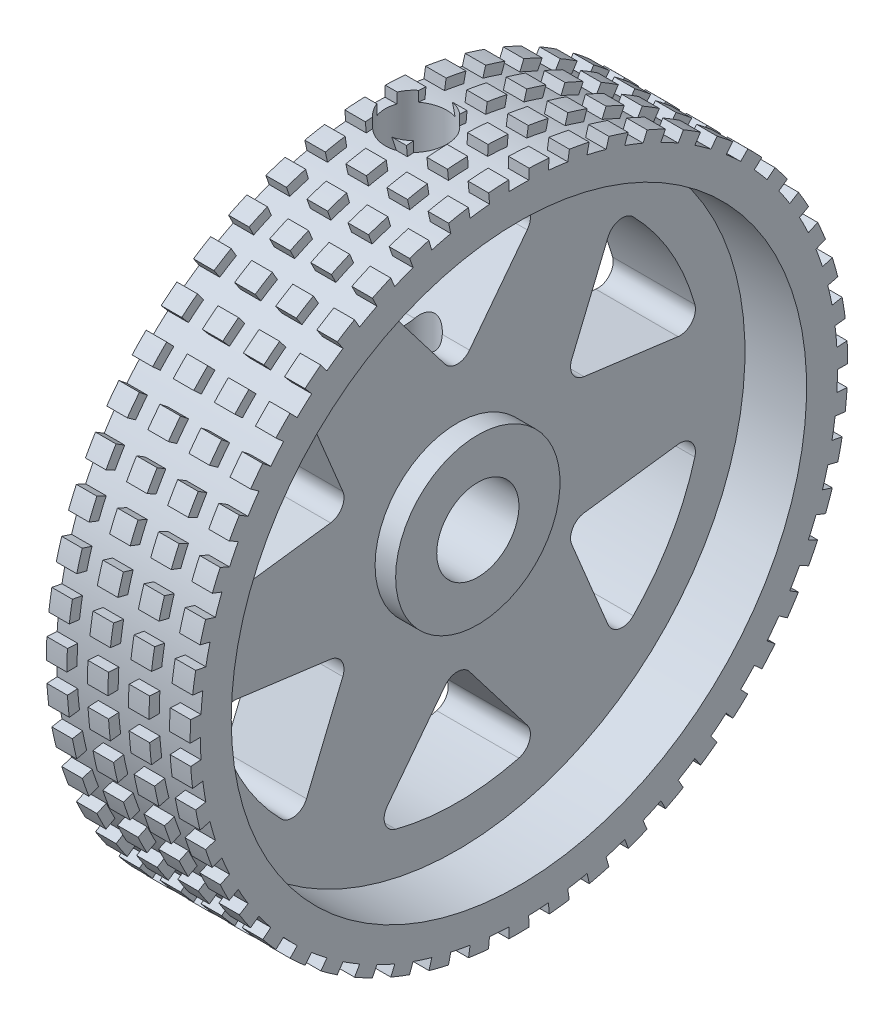
SolidWorks part; units mm, degrees
ref_plane "Front Plane" through (0, 0, 0) normal (0, 0, 1) x (1, 0, 0)
ref_plane "Top Plane" through (0, 0, 0) normal (0, 1, 0) x (1, 0, 0)
ref_plane "Right Plane" through (0, 0, 0) normal (1, 0, 0) x (0, 0, -1)
sketch "Sketch1" plane through (0, 0, 0) normal (0, 0, 1) x (1, 0, 0)
  line L4 (4, 4) -> (4, 14)
  line L7 (4, 4) -> (5, 4)
  line L8 (5, 2) -> (5, 4)
  line L11 (4, 14) -> (7, 14)
  line L12 (7, 16) -> (7, 14)
  line L15 (0, 16) -> (7, 16)
  line L16 (5, 2) -> (0, 2)
  line L17 (0, 16) -> (0, 2)
  line L18 (0, 0) -> (14.3694, 0) construction
  dimension "D1" = 2
  dimension "D2" = 5
  dimension "D3" = 7
  dimension "D4" = 4
  dimension "D5" = 4
  dimension "D6" = 14
  dimension "D7" = 16
revolve "Revolve1" add sketch "Sketch1" angle 360 about L18
sketch "Sketch2" plane through (0, 0, 0) normal (0, 0, 1) x (1, 0, 0)
  line L0 (2, 0) -> (2, 16)
  line L1 (7, 16) -> (0, 16) construction
  line L2 (2, 16) -> (3.5, 16)
  line L3 (3.5, 16) -> (3.5, 11.5)
  line L4 (3.5, 11.5) -> (2.9, 11.5)
  line L5 (2.9, 11.5) -> (2.9, 0)
  line L6 (2.9, 0) -> (2, 0)
  dimension "D1" = 1.5
  dimension "D2" = 4.5
  dimension "D3" = 0.9
revolve "Cut-Revolve1" cut sketch "Sketch2" angle 360 about L0
sketch "Sketch3" plane through (4, 0, 0) normal (1, 0, 0) x (0, 0, -1)
  line L0 (0, 6) -> (0, 12) construction
  line L1 (-0.595, 6.7754) -> (-3.4046, 10.4369)
  line L2 (0.595, 6.7754) -> (3.4046, 10.4369)
  arc A1 (2.9969, 11.6198) -> (-2.9969, 11.6198) centre (0, 0) ccw
  arc A2 (3.4046, 10.4369) -> (2.9969, 11.6198) centre (2.8096, 10.8935) ccw
  arc A3 (-0.595, 6.7754) -> (0.595, 6.7754) centre (0, 7.232) ccw
  arc A4 (-3.4046, 10.4369) -> (-2.9969, 11.6198) centre (-2.8096, 10.8935) cw
  dimension "D1" = 24
  dimension "D2" = 0.75
  dimension "D3" = 75
extrude "Cut-Extrude1" cut sketch "Sketch3" against normal through all
pattern_circular "CirPattern1" count 6 over 360 about axis through (0, 0, 0) along (-1, 0, 0) of "Cut-Extrude1"
sketch "Sketch4" plane through (0, 0, 0) normal (0, 0, 1) x (1, 0, 0)
  line L5 (7, 16) -> (3.5, 16) construction
  line L6 (6, 16) -> (5, 16)
  line L7 (6, 16) -> (6, 15.5)
  line L8 (6, 15.5) -> (5, 15.5)
  line L9 (5, 16) -> (5, 15.5)
  line L10 (7, -16) -> (7, 16) construction
  dimension "D1" = 1
  dimension "D2" = 0.5
  dimension "D3" = 1
revolve "Cut-Revolve2" cut sketch "Sketch4" angle 360 about axis through (0, 0, 0) along (-1, 0, 0)
sketch "Sketch6" plane through (0, 0, 0) normal (0, 0, 1) x (1, 0, 0)
  line L1 (7.0185, 16) -> (0, 16)
  line L2 (7.0185, 16) -> (7.0185, 15.5)
  line L3 (7.0185, 15.5) -> (0, 15.5)
  line L4 (0, 16) -> (0, 15.5)
  line L5 (5, 16) -> (3.4999, 16) construction
  dimension "D1" = 0.5
  dimension "D2" = 0
revolve "Cut-Revolve3" cut sketch "Sketch6" angle 3.55 mid plane about axis through (0, 0, 0) along (-1, 0, 0)
pattern_linear "LPattern1" count 3 spacing 2 along (-1, 0, 0) of "Cut-Revolve2"
pattern_circular "CirPattern2" count 51 over 360 about axis through (0, 0, 0) along (-1, 0, 0) of "Cut-Revolve3"
